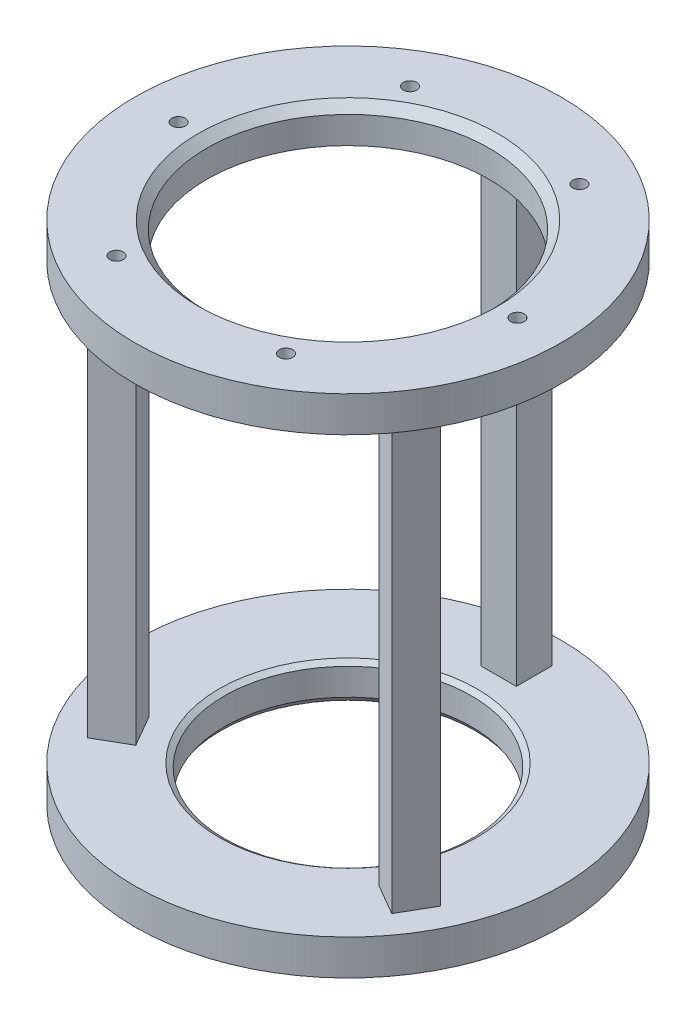
SolidWorks part; units mm, degrees
ref_plane "Front Plane" through (0, 0, 0) normal (0, 0, 1) x (1, 0, 0)
ref_plane "Top Plane" through (0, 0, 0) normal (0, 1, 0) x (1, 0, 0)
ref_plane "Right Plane" through (0, 0, 0) normal (1, 0, 0) x (0, 0, -1)
sketch "Sketch1" plane through (0, 0, 0) normal (0, 1, 0) x (1, 0, 0)
  line L0 (0, 0) -> (30.3054, 52.4905) construction
  line L1 (0, 44.2277) -> (0, 76.2)
  line L2 (-6.35, 53.8639) -> (6.35, 53.8639)
  line L3 (-6.35, 53.8639) -> (-6.35, 66.5639)
  line L4 (-6.35, 66.5639) -> (6.35, 66.5639)
  line L5 (6.35, 53.8639) -> (6.35, 66.5639)
  line L6 (-6.35, 53.8639) -> (6.35, 66.5639) construction
  line L7 (-6.35, 66.5639) -> (6.35, 53.8639) construction
  line L8 (49.8225, -21.4327) -> (60.821, -27.7827)
  line L9 (49.8225, -21.4327) -> (43.4725, -32.4312)
  line L10 (43.4725, -32.4312) -> (54.471, -38.7812)
  line L11 (60.821, -27.7827) -> (54.471, -38.7812)
  line L12 (-43.4725, -32.4312) -> (-54.471, -38.7812)
  line L13 (-43.4725, -32.4312) -> (-49.8225, -21.4327)
  line L14 (-49.8225, -21.4327) -> (-60.821, -27.7827)
  line L15 (-54.471, -38.7812) -> (-60.821, -27.7827)
  line L16 (-4.699, 55.5149) -> (-4.699, 64.9129)
  line L17 (-4.699, 64.9129) -> (4.699, 64.9129)
  line L18 (4.699, 55.5149) -> (4.699, 64.9129)
  line L19 (-4.699, 55.5149) -> (4.699, 55.5149)
  line L20 (50.4268, -23.688) -> (58.5657, -28.387)
  line L21 (58.5657, -28.387) -> (53.8667, -36.5259)
  line L22 (45.7278, -31.8269) -> (53.8667, -36.5259)
  line L23 (50.4268, -23.688) -> (45.7278, -31.8269)
  line L24 (-45.7278, -31.8269) -> (-53.8667, -36.5259)
  line L25 (-53.8667, -36.5259) -> (-58.5657, -28.387)
  line L26 (-50.4268, -23.688) -> (-58.5657, -28.387)
  line L27 (-45.7278, -31.8269) -> (-50.4268, -23.688)
  circle A0 centre (0, 0) radius 76.2
  circle A3 centre (0, 0) radius 68.8721 construction
  circle A4 centre (0, 0) radius 44.2278
  circle A6 centre (30.3054, 52.4905) radius 2.413
  circle A7 centre (60.6109, 0) radius 2.413
  circle A8 centre (30.3054, -52.4905) radius 2.413
  circle A9 centre (-30.3054, -52.4905) radius 2.413
  circle A10 centre (-60.6109, 0) radius 2.413
  circle A11 centre (-30.3054, 52.4905) radius 2.413
  circle A12 centre (0, 0) radius 60.6109 construction
  point P6 (0, 60.2139)
  point P28 (0, 0)
  point P37 (0, 0)
  point P51 (0, 0)
  dimension "D1" = 152.4
  dimension "D2" = 137.7442
  dimension "D7" = 4.826
  dimension "D12" = 121.2217
  dimension "D3" = 88.4555
  dimension "D4" = 12.7
  dimension "D5" = 12.7
  dimension "D10" = 1.651
  dimension "D8" = 6
  dimension "D9" = 3
  dimension "D11" = 3
extrude "Boss-Extrude1" add sketch "Sketch1" against normal blind 12.7 contours A4 L2 L3 L4 A0 L5 A11 A10 A9 A8 A7 A6 L12 L15 L14 L13 L8 L11 L10 L9 | L24 L27 L26 L25 | L15 L12 L13 L14 L27 L24 L25 L26 | A10 | A9 | A11 | L16 L19 L1 L17 | L1 L19 L18 L17 | L19 L1 L2 L5 L4 L17 L18 | L19 L16 L17 L1 L4 L3 L2 | A6 | A7 | L20 L23 L22 L21 | L11 L8 L9 L10 L23 L20 L21 L22 | A8 region at (52.3575, 0, -52.3575) region at (-3.175, 0, -54.0059) region at (0.142, 0, -54.6894) region at (-2.3495, 0, -60.2139) region at (2.3495, 0, -60.2139) region at (55.1991, 0, 24.8202) region at (-49.0944, 0, 35.3937) region at (52.1467, 0, 30.1069) region at (-52.1467, 0, 30.1069) region at (30.3054, 0, -52.4905) region at (60.6109, 0, 0) region at (30.3054, 0, 52.4905) region at (-30.3054, 0, 52.4905) region at (-60.6109, 0, 0) region at (-30.3054, 0, -52.4905)
extrude "Boss-Extrude2" add sketch "Sketch1<5>" along normal blind 155.575 separate body contours L11 L8 L9 L10 L23 L20 L21 L22 | L15 L12 L13 L14 L27 L24 L25 L26 | L19 L1 L2 L5 L4 L17 L18 | L19 L16 L17 L1 L4 L3 L2 region at (-3.175, 0, -54.0059) region at (0.142, 0, -54.6894) region at (55.1991, 0, 24.8202) region at (-49.0944, 0, 35.3937)
sketch "Sketch1<5>" plane through (0, 0, 0) normal (0, 1, 0) x (1, 0, 0) same geometry as "Sketch1"
ref_plane "Plane2" through (0, 155.575, 0) normal (0, 1, 0) x (1, 0, 0)
sketch "Sketch2" plane through (0, 155.575, 0) normal (0, 1, 0) x (1, 0, 0)
  circle A0 centre (0, 0) radius 76.2 construction
  circle A1 centre (30.3054, -52.4905) radius 2.413 construction
  circle A2 centre (-30.3054, 52.4905) radius 2.413 construction
  circle A3 centre (-60.6109, 0) radius 2.413 construction
  circle A4 centre (-30.3054, -52.4905) radius 2.413 construction
  circle A5 centre (60.6109, 0) radius 2.413 construction
  circle A6 centre (30.3054, 52.4905) radius 2.413 construction
  circle A8 centre (0, 0) radius 76.2
  circle A9 centre (30.3054, -52.4905) radius 2.413
  circle A10 centre (-30.3054, 52.4905) radius 2.413
  circle A11 centre (-60.6109, 0) radius 2.413
  circle A12 centre (-30.3054, -52.4905) radius 2.413
  circle A13 centre (60.6109, 0) radius 2.413
  circle A14 centre (30.3054, 52.4905) radius 2.413
  circle A16 centre (0, 0) radius 50.5206
  point P0 (60.6109, 0)
  point P2 (30.3054, 52.4905)
  point P4 (-30.3054, -52.4905)
extrude "Boss-Extrude3" add sketch "Sketch2" along normal blind 12.7
chamfer "Chamfer1" distance 3.0353 angle 45 1 edges at (0, 168.275, 50.5206)
chamfer "Chamfer2" distance 1.8542 distance2 1.2827 1 edges at (0, 0, 44.2278) first distance on face at (0, 0, 76.2)
chamfer "Chamfer3" distance 1.8542 distance2 1.2827 1 edges at (0, -12.7, 44.2278) first distance on face at (0, -1.2827, 44.2278)
